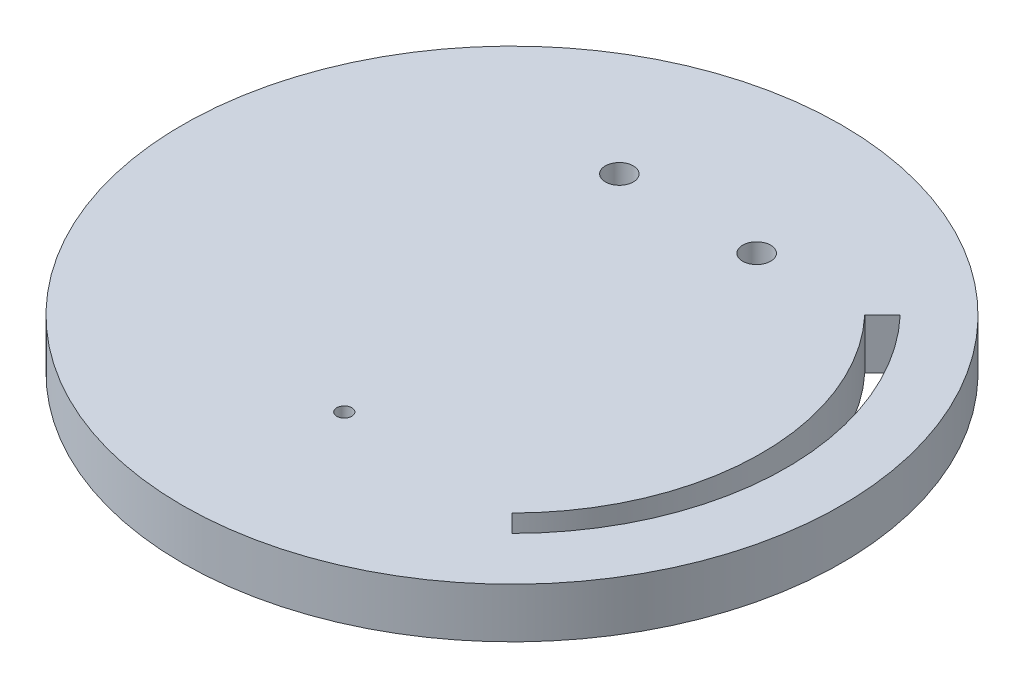
SolidWorks part; units mm, degrees
material "6061-T6 (SS)"
ref_plane "Front" through (0, 0, 0) normal (0, 0, 1) x (1, 0, 0)
ref_plane "Top" through (0, 0, 0) normal (0, 1, 0) x (1, 0, 0)
ref_plane "Right" through (0, 0, 0) normal (1, 0, 0) x (0, 0, -1)
sketch "Sketch1" plane through (0, 0, 0) normal (0, 1, 0) x (1, 0, 0)
  line L1 (0, 0) -> (127.635, 0)
  line L2 (0, 0) -> (0, 127.635)
  line L3 (0, 127.635) -> (127.635, 127.635)
  line L4 (127.635, 0) -> (127.635, 127.635)
  dimension "D1" = 127.635
  dimension "D2" = 127.635
extrude "Main Plate" add sketch "Sketch1" along normal blind 12.7
sketch "Sketch9" plane through (0, 12.7, 0) normal (0, 1, 0) x (1, 0, 0)
  circle A0 centre (63.8175, 63.8175) radius 85.725
  dimension "D1" = 171.45
extrude "Boss-Extrude1" add sketch "Sketch9" against normal up to surface (12.7 mm away) contours A0 up to face at (63.8175, 0, -63.8175)
sketch "Sketch10" plane through (0, 12.7, 0) normal (0, 1, 0) x (1, 0, 0)
  circle A0 centre (63.8175, 63.8175) radius 97.0396
  circle A1 centre (63.8175, 63.8175) radius 83.82
extrude "Cut-Extrude1" cut sketch "Sketch10" against normal blind 167.64 contours A0 | A1
sketch "Sketch11" plane through (0, 12.7, 0) normal (0, 1, 0) x (1, 0, 0)
  circle A0 centre (63.8175, 63.8175) radius 38.4175 construction
  circle A1 centre (63.8175, 63.8175) radius 42.8813 construction
  circle A2 centre (63.8175, 63.8175) radius 48.0528 construction
  circle A3 centre (63.8175, 63.8175) radius 83.82 construction
  dimension "D1" = 76.835
  dimension "D2" = 85.7626
  dimension "D3" = 96.1055
sketch "Sketch12" plane through (0, 12.7, 0) normal (0, 1, 0) x (1, 0, 0)
  line L0 (63.8175, 156.3529) -> (63.8175, -30.2474) construction
  line L1 (160.3603, 63.0527) -> (-31.9911, 63.0527) construction
  point P6 (63.8175, 63.0527)
sketch "Sketch2" plane through (0, 12.7, 0) normal (0, 1, 0) x (1, 0, 0)
  circle A0 centre (46.355, 108.585) radius 3.556
  circle A3 centre (63.8175, 63.8175) radius 48.0528 construction
  dimension "D1" = 7.112
extrude "U-Bolt Hole" cut sketch "Sketch2" against normal blind 12.7
pattern_linear "U-Bolt Pattern" count 2 spacing 34.925 along (1, 0, 0) of "U-Bolt Hole"
sketch "Sketch3" [suppressed] plane through (0, 12.7, 0) normal (0, 1, 0) x (1, 0, 0)
  circle A0 centre (25.4, 44.7675) radius 1.778
  circle A1 centre (63.8175, 63.8175) radius 42.8813 construction
  dimension "D1" = 3.556
extrude "Raptor Bolt Hole" [suppressed] cut sketch "Sketch3" against normal blind 12.7
pattern_linear "Raptor Bolt Pattern" [suppressed] count 2 spacing 38.1 along (0, 0, -1) count 2 spacing 76.835 along (1, 0, 0) of bodies 104
sketch "Sketch4" [suppressed] plane through (0, 12.7, 0) normal (0, 1, 0) x (1, 0, 0)
  circle A0 centre (25.4, 63.8175) radius 12.7
  circle A1 centre (63.8175, 63.8175) radius 38.4175 construction
  dimension "D1" = 25.4
extrude "Co2 Cylinder Hole" [suppressed] cut sketch "Sketch4" against normal blind 12.7
pattern_linear "Co2 Pattern" [suppressed] count 2 spacing 76.835 along (1, 0, 0) of bodies 106
sketch "Sketch13" plane through (0, 12.7, 0) normal (0, 1, 0) x (1, 0, 0)
  line L0 (63.8175, 156.3529) -> (63.8175, -30.2474) construction
  circle A0 centre (63.8175, 21.1558) radius 1.905
  dimension "D1" = 3.81
extrude "Cut-Extrude2" cut sketch "Sketch13" against normal up to surface (12.7 mm away) up to face at (81.28, 0, -105.029)
sketch "Sketch14" plane through (0, 12.7, 0) normal (0, 1, 0) x (1, 0, 0)
  line L0 (201.1692, 63.8175) -> (-73.4523, 63.8175) construction
ref_plane "Plane1" through (0, 0, -63.8175) normal (0, 0, -1) x (-1, 0, 0)
ref_plane "Plane2" through (-20.0025, 0, 0) normal (-1, 0, 0) x (0, 0, 1)
sketch "Sketch15" plane through (-20.0025, 0, 0) normal (-1, 0, 0) x (0, 0, 1)
  line L0 (-63.8175, 92.202) -> (-63.8175, -92.202) construction
  line L1 (20.0025, 12.7) -> (-147.6375, 12.7) construction
  circle A0 centre (-63.8175, 6.35) radius 1.4351
  dimension "D1" = 2.8702
  dimension "D2" = 6.35
extrude "Cut-Extrude3" [suppressed] cut sketch "Sketch15" against normal blind 15.24
pattern_circular "CirPattern1" [suppressed] count 12 over 360 reverse direction yes of bodies 115
sketch "Sketch16" plane through (0, 12.7, 0) normal (0, 1, 0) x (1, 0, 0)
  line L0 (63.8175, 63.8175) -> (123.0872, 123.0872) construction
  line L1 (63.8175, 63.8175) -> (123.0872, 4.5478) construction
  line L2 (92.202, 63.8175) -> (-92.202, 63.8175) construction
  line L3 (107.3987, 20.2363) -> (111.8888, 15.7462)
  line L4 (108.6773, 108.6773) -> (113.1913, 113.1913)
  circle A0 centre (63.8175, 63.8175) radius 83.82 construction
  arc A1 (113.1913, 113.1913) -> (111.8888, 15.7462) centre (62.4974, 65.1376) cw
  arc A2 (108.6773, 108.6773) -> (107.3987, 20.2363) centre (62.4754, 65.1156) cw
  dimension "D3" = 69.85
  dimension "D4" = 63.5
  dimension "D1" = 45
  dimension "D2" = 90
  dimension "D5" = 6.35
  dimension "D6" = 6.3837
extrude "Cut-Extrude4" cut sketch "Sketch16" against normal blind 15.24
